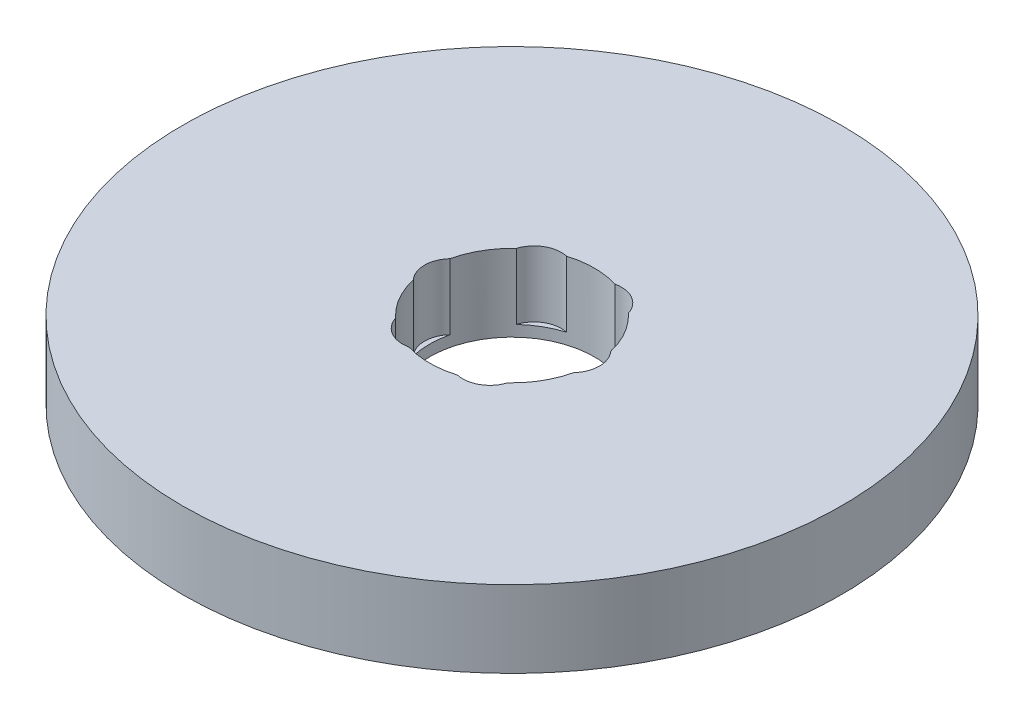
SolidWorks part; units mm, degrees
ref_plane "Front Plane" through (0, 0, 0) normal (0, 0, 1) x (1, 0, 0)
ref_plane "Top Plane" through (0, 0, 0) normal (0, 1, 0) x (1, 0, 0)
ref_plane "Right Plane" through (0, 0, 0) normal (1, 0, 0) x (0, 0, -1)
sketch "Sketch1" plane through (0, 0, 0) normal (0, 1, 0) x (1, 0, 0)
  circle A0 centre (0, 0) radius 90
  dimension "FLANGE_OD" = 180
extrude "Boss-Extrude1" add sketch "Sketch1" along normal blind 21
sketch "Sketch2" plane through (0, 0, 0) normal (0, 1, 0) x (1, 0, 0)
  circle A0 centre (0, 0) radius 22.5
  dimension "BORE_D" = 45
extrude "Cut-Extrude1" cut sketch "Sketch2" along normal through all
sketch "Sketch3" plane through (0, 21, 0) normal (0, 1, 0) x (1, 0, 0)
  circle A0 centre (0, 0) radius 16.4579 construction
  circle A1 centre (-16.4579, 0) radius 7.43
  dimension "BOLT_D" = 14.8601
  dimension "BOLT_PCD" = 32.9159
extrude "Cut-Extrude2" cut sketch "Sketch3" against normal blind 17.9877
pattern_circular "CirPattern1" count 6 over 360 about axis through (0, 0, 0) along (0, 1, 0) of "Cut-Extrude2"
